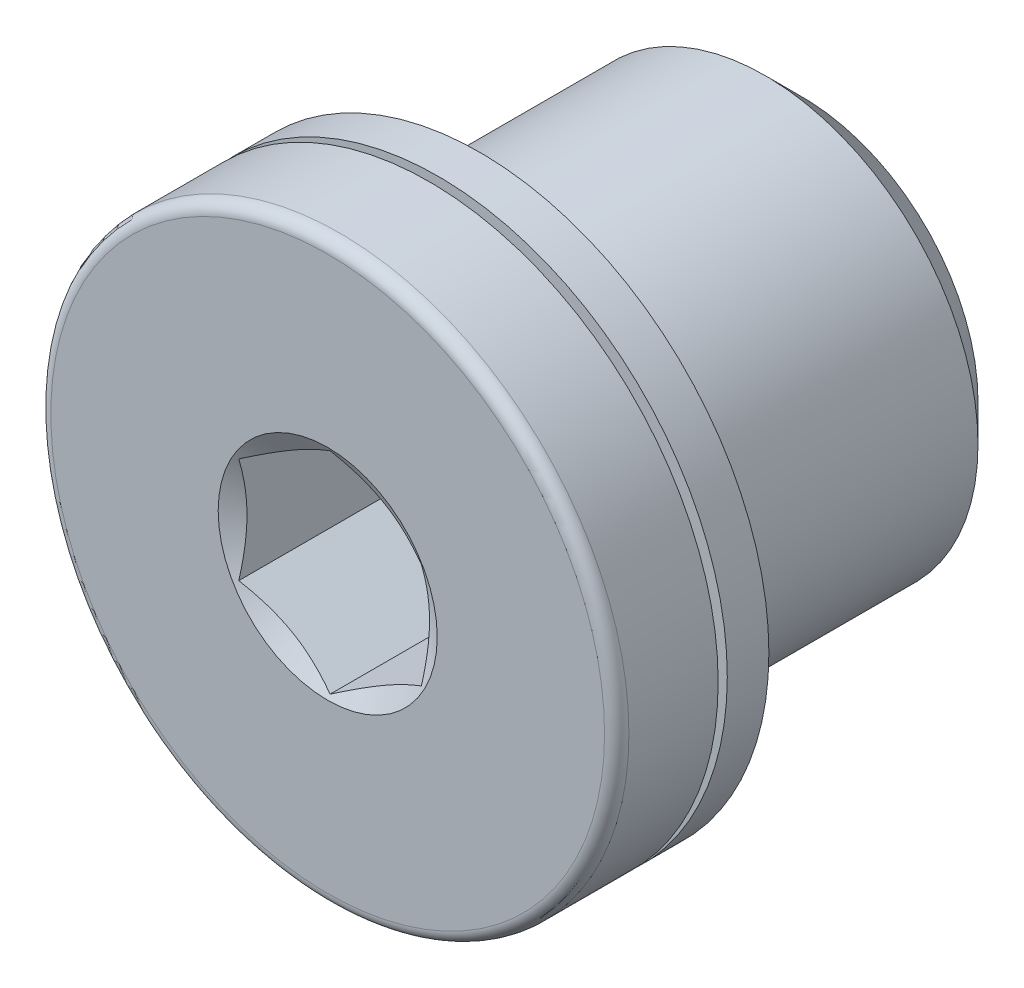
SolidWorks part; units mm, degrees
ref_plane "Front Plane" through (0, 0, 0) normal (0, 0, 1) x (1, 0, 0)
ref_plane "Top Plane" through (0, 0, 0) normal (0, 1, 0) x (1, 0, 0)
ref_plane "Right Plane" through (0, 0, 0) normal (1, 0, 0) x (0, 0, -1)
sketch "Sketch1" plane through (0, 0, 0) normal (1, 0, 0) x (0, 0, -1)
  line L0 (-1.4608, 0) -> (-2.5, 1.8)
  line L1 (-2.5, 1.8) -> (-2.5, 4.55)
  line L2 (-2.3, 4.75) -> (-0.8333, 4.75)
  line L3 (-0.8333, 4.75) -> (-0.8333, 4.275)
  line L4 (-0.8333, 4.275) -> (-0.6833, 4.275)
  line L5 (-0.6833, 4.275) -> (-0.6833, 4.75)
  line L6 (-0.6833, 4.75) -> (0, 4.75)
  line L7 (0, 4.75) -> (0, 2.8865)
  line L8 (0, 2.8865) -> (0.6135, 3.5)
  line L9 (0.6135, 3.5) -> (4.6865, 3.5)
  line L10 (4.6865, 3.5) -> (5.3, 2.8865)
  line L11 (5.3, 2.8865) -> (5.3, 0)
  line L12 (5.3, 0) -> (-1.4608, 0)
  line L13 (5.3, 0) -> (-1.4608, 0) construction
  arc A0 (-2.5, 4.55) -> (-2.3, 4.75) centre (-2.3, 4.55) cw
revolve "Revolve1" add sketch "Sketch1" angle 360 about L13 reverse direction yes
cosmetic thread "Cosmetic Thread1" parameters "D1"=5.3, "D2"=5.773
ref_plane "Plane1" through (0, 0, 2.5) normal (0, 0, 1) x (1, 0, 0)
sketch "Sketch2" plane through (0, 0, 2.5) normal (0, 0, 1) x (1, 0, 0)
  line L0 (-1.5, -0.866) -> (0, -1.7321)
  line L1 (0, -1.7321) -> (1.5, -0.866)
  line L2 (1.5, -0.866) -> (1.5, 0.866)
  line L3 (1.5, 0.866) -> (0, 1.7321)
  line L4 (0, 1.7321) -> (-1.5, 0.866)
  line L5 (-1.5, 0.866) -> (-1.5, -0.866)
extrude "Cut-Extrude1" cut sketch "Sketch2" against normal blind 2.5
ref_plane "ANBAU XY" through (0, 0, 0) normal (0, 0, 1) x (1, 0, 0)
ref_plane "ANBAU XZ" through (0, 0, 0) normal (0, -1, 0) x (-1, 0, 0)
ref_plane "ANBAU YZ" through (0, 0, 0) normal (1, 0, 0) x (0, 0, -1)
ref_axis "ANBAU X" through (-80.9, 0, 0) along (1, 0, 0)
ref_axis "ANBAU Y" through (0, -50, 0) along (0, 1, 0)
ref_axis "ANBAU Z" through (0, 0, 80.9) along (0, 0, -1)
sketch3d "ANBAU"
  point P0 (0, 0, 0)
ref_plane "ANBAU_STD XY" through (0, 0, 0) normal (0, 0, 1) x (1, 0, 0)
ref_plane "ANBAU_STD XZ" through (0, 0, 0) normal (0, -1, 0) x (-1, 0, 0)
ref_plane "ANBAU_STD YZ" through (0, 0, 0) normal (1, 0, 0) x (0, 0, -1)
ref_axis "ANBAU_STD X" through (-80.9, 0, 0) along (1, 0, 0)
ref_axis "ANBAU_STD Y" through (0, -50, 0) along (0, 1, 0)
ref_axis "ANBAU_STD Z" through (0, 0, 80.9) along (0, 0, -1)
sketch3d "ANBAU_STD"
  point P0 (0, 0, 0)
